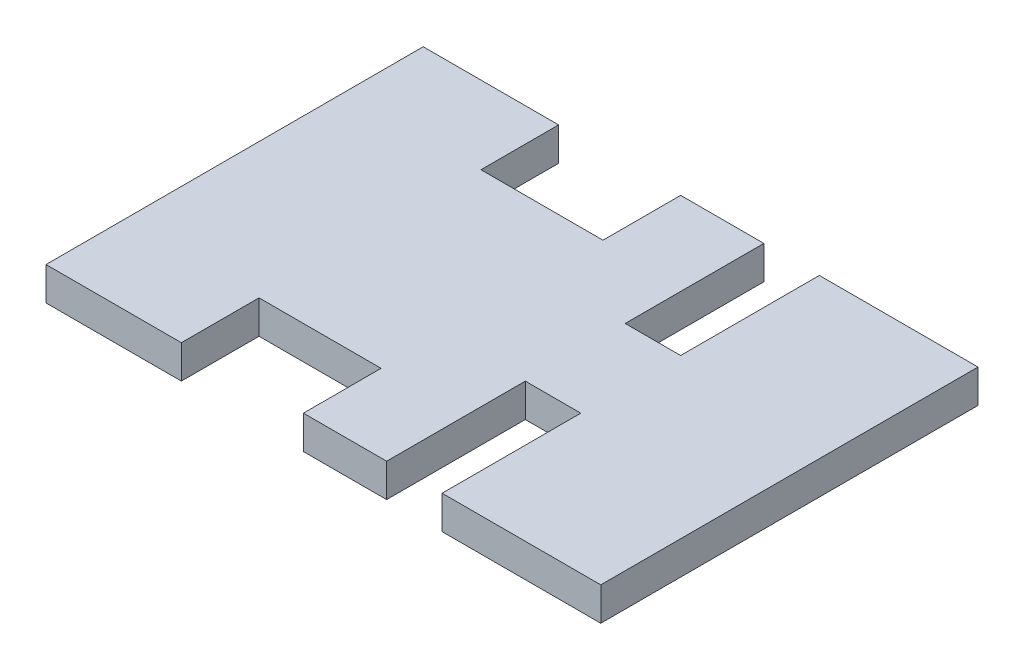
SolidWorks part; units mm, degrees
material "Maple"
ref_plane "Front Plane" through (0, 0, 0) normal (0, 0, 1) x (1, 0, 0)
ref_plane "Top Plane" through (0, 0, 0) normal (0, 1, 0) x (1, 0, 0)
ref_plane "Right Plane" through (0, 0, 0) normal (1, 0, 0) x (0, 0, -1)
sketch "Sketch1" plane through (0, 0, 0) normal (0, 1, 0) x (1, 0, 0)
  line L1 (-50, 34) -> (50, 34)
  line L2 (-50, 34) -> (-50, -34)
  line L3 (-50, -34) -> (50, -34)
  line L4 (50, 34) -> (50, -34)
  line L5 (-50, 34) -> (50, -34) construction
  line L6 (-50, -34) -> (50, 34) construction
  point P0 (0, 0)
  dimension "D1" = 100
  dimension "D2" = 68
extrude "Boss-Extrude1" add sketch "Sketch1" along normal blind 6
ref_plane "Plane1" through (0, 3, 0) normal (0, 1, 0) x (1, 0, 0)
sketch "Sketch2" plane through (0, 0, 0) normal (0, -1, 0) x (1, 0, 0)
  line L0 (16.4, -34) -> (16.4, 34) construction
  line L1 (50, -34) -> (-50, -34) construction
  line L2 (-50, 34) -> (50, 34) construction
  line L4 (21.4, -34) -> (11.4, -34)
  line L5 (21.4, -34) -> (21.4, -9)
  line L6 (21.4, -9) -> (11.4, -9)
  line L7 (11.4, -34) -> (11.4, -9)
  dimension "D1" = 10
  dimension "D2" = 25
extrude "Cut-Extrude1" cut sketch "Sketch2" against normal through all
sketch "Sketch3" plane through (0, 0, 0) normal (0, -1, 0) x (1, 0, 0)
  line L0 (11.4, -34) -> (-50, -34) construction
  line L1 (-25.6, -34) -> (-3.6, -34)
  line L2 (-25.6, -34) -> (-25.6, -20)
  line L3 (-25.6, -20) -> (-3.6, -20)
  line L4 (-3.6, -34) -> (-3.6, -20)
  line L7 (-14.6, -20.5) -> (-14.6, -34) construction
  line L8 (-9.5, -20.5) -> (-19.7, -20.5) construction
  dimension "D1" = 22
  dimension "D2" = 14
extrude "Cut-Extrude2" cut sketch "Sketch3" against normal through all contours L3 L4 L1 L2
mirror "Mirror1" about plane through (0, 0, 0) normal (0, 0, 1) of "Cut-Extrude2", "Cut-Extrude1"
sketch "Sketch5" plane through (0, 0, 0) normal (0, -1, 0) x (1, 0, 0)
  line L1 (50, -34) -> (11.4, -34)
  line L2 (50, -34) -> (50, 34)
  line L3 (50, 34) -> (11.4, 34)
  line L4 (11.4, -34) -> (11.4, 34)
extrude "Cut-Extrude4" [suppressed] cut sketch "Sketch5" against normal through all
